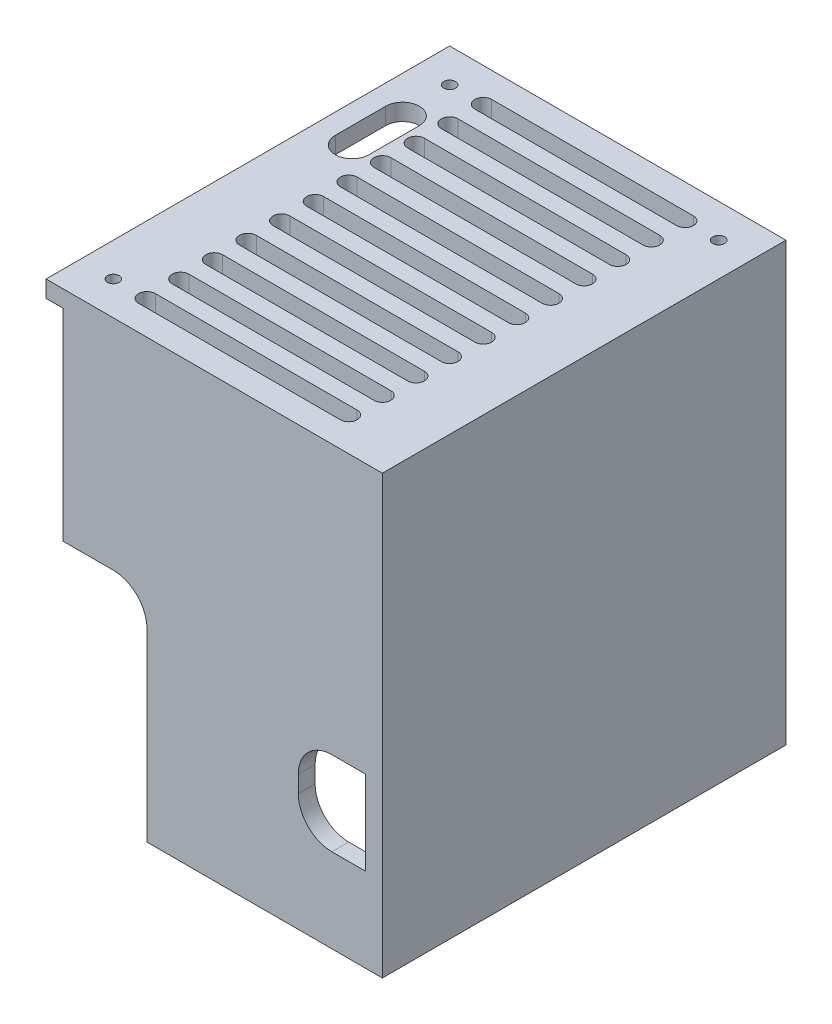
SolidWorks part; units mm, degrees
ref_plane "Front Plane" through (0, 0, 0) normal (0, 0, 1) x (1, 0, 0)
ref_plane "Top Plane" through (0, 0, 0) normal (0, 1, 0) x (1, 0, 0)
ref_plane "Right Plane" through (0, 0, 0) normal (1, 0, 0) x (0, 0, -1)
sketch "Sketch2" plane through (0, 0, 0) normal (0, 1, 0) x (1, 0, 0)
  line L1 (0, 0) -> (100, 0)
  line L2 (0, 0) -> (0, 120)
  line L3 (0, 120) -> (100, 120)
  line L4 (100, 0) -> (100, 120)
  line L5 (0, 0) -> (100, 120) construction
  line L6 (0, 120) -> (100, 0) construction
  point P4 (50, 60)
  dimension "D1" = 100
  dimension "D2" = 120
extrude "Boss-Extrude1" add sketch "Sketch2" along normal blind 5
sketch "Sketch3" plane through (0, 0, 0) normal (0, -1, 0) x (1, 0, 0)
  line L0 (0, 0) -> (100, 0) construction
  line L1 (100, 0) -> (95, 0)
  line L2 (100, 0) -> (100, -120)
  line L3 (100, -120) -> (95, -120)
  line L4 (95, 0) -> (95, -120)
  line L5 (100, 0) -> (95, -120) construction
  line L6 (100, -120) -> (95, 0) construction
  line L7 (100, -120) -> (0, -120) construction
  line L8 (100, 0) -> (100, -120) construction
  point P4 (97.5, -60)
  dimension "D1" = 5
extrude "Boss-Extrude2" add sketch "Sketch3" along normal blind 125
sketch "Sketch4" plane through (0, 0, 0) normal (0, -1, 0) x (1, 0, 0)
  line L0 (0, 0) -> (95, 0) construction
  line L1 (95, 0) -> (5, 0)
  line L2 (95, 0) -> (95, -5)
  line L3 (95, -5) -> (5, -5)
  line L4 (5, 0) -> (5, -5)
  line L5 (95, 0) -> (5, -5) construction
  line L6 (95, -5) -> (5, 0) construction
  line L7 (95, 0) -> (95, -120) construction
  point P4 (50, -2.5)
  dimension "D1" = 5
  dimension "D2" = 90
extrude "Boss-Extrude3" add sketch "Sketch4" along normal blind 125
sketch "Sketch5" plane through (0, -125, 0) normal (0, -1, 0) x (1, 0, 0)
  line L0 (95, -5) -> (95, -120) construction
  line L1 (95, -5) -> (85, -5)
  line L2 (95, -5) -> (95, -15)
  line L3 (95, -15) -> (85, -15)
  line L4 (85, -5) -> (85, -15)
  line L5 (95, -5) -> (85, -15) construction
  line L6 (95, -15) -> (85, -5) construction
  line L7 (5, -5) -> (95, -5) construction
  line L8 (95, -5) -> (95, -120) construction
  line L9 (95, -115) -> (85, -115)
  line L10 (95, -115) -> (95, -105)
  line L11 (95, -105) -> (85, -105)
  line L12 (85, -115) -> (85, -105)
  line L13 (95, -115) -> (85, -105) construction
  line L14 (95, -105) -> (85, -115) construction
  line L15 (95, -120) -> (0, -120) construction
  point P4 (90, -10)
  point P13 (90, -110)
  dimension "D1" = 10
  dimension "D2" = 10
  dimension "D3" = 10
  dimension "D4" = 10
  dimension "D5" = 5
extrude "Boss-Extrude4" add sketch "Sketch5" against normal blind 15
sketch "Sketch6" plane through (0, -125, 0) normal (0, -1, 0) x (1, 0, 0)
  line L0 (85, -15) -> (95, -15) construction
  line L1 (85, -5) -> (85, -15) construction
  line L2 (95, -105) -> (85, -105) construction
  line L3 (85, -105) -> (85, -115) construction
  circle A0 centre (90, -10) radius 1.45
  circle A1 centre (90, -110) radius 1.45
  dimension "D1" = 2.9
  dimension "D2" = 5
  dimension "D3" = 5
  dimension "D4" = 5
  dimension "D5" = 5
extrude "Cut-Extrude1" cut sketch "Sketch6" against normal blind 10
chamfer "Chamfer1" distance 10 angle 45 2 edges at (95, -110, -110) (95, -110, -10)
sketch "Sketch7" plane through (0, 0, 0) normal (0, -1, 0) x (1, 0, 0)
  line L0 (20, -10) -> (80, -10) construction
  line L1 (20, -7.5) -> (80, -7.5)
  line L2 (20, -12.5) -> (80, -12.5)
  line L3 (5, -5) -> (95, -5) construction
  line L4 (85, -5) -> (85, -15) construction
  line L5 (20, -20) -> (80, -20) construction
  line L6 (20, -17.5) -> (80, -17.5)
  line L7 (20, -22.5) -> (80, -22.5)
  line L8 (20, -30) -> (80, -30) construction
  line L9 (20, -27.5) -> (80, -27.5)
  line L10 (20, -32.5) -> (80, -32.5)
  line L11 (20, -40) -> (80, -40) construction
  line L12 (20, -37.5) -> (80, -37.5)
  line L13 (20, -42.5) -> (80, -42.5)
  line L14 (20, -50) -> (80, -50) construction
  line L15 (20, -47.5) -> (80, -47.5)
  line L16 (20, -52.5) -> (80, -52.5)
  line L17 (20, -60) -> (80, -60) construction
  line L18 (20, -57.5) -> (80, -57.5)
  line L19 (20, -62.5) -> (80, -62.5)
  line L20 (20, -70) -> (80, -70) construction
  line L21 (20, -67.5) -> (80, -67.5)
  line L22 (20, -72.5) -> (80, -72.5)
  line L23 (20, -80) -> (80, -80) construction
  line L24 (20, -77.5) -> (80, -77.5)
  line L25 (20, -82.5) -> (80, -82.5)
  line L26 (20, -90) -> (80, -90) construction
  line L27 (20, -87.5) -> (80, -87.5)
  line L28 (20, -92.5) -> (80, -92.5)
  line L29 (20, -100) -> (80, -100) construction
  line L30 (20, -97.5) -> (80, -97.5)
  line L31 (20, -102.5) -> (80, -102.5)
  line L32 (20, -110) -> (80, -110) construction
  line L33 (20, -107.5) -> (80, -107.5)
  line L34 (20, -112.5) -> (80, -112.5)
  line L35 (20, -10) -> (20, -20) construction
  arc A0 (20, -7.5) -> (20, -12.5) centre (20, -10) ccw
  arc A1 (80, -12.5) -> (80, -7.5) centre (80, -10) ccw
  arc A2 (20, -17.5) -> (20, -22.5) centre (20, -20) ccw
  arc A3 (80, -22.5) -> (80, -17.5) centre (80, -20) ccw
  arc A4 (20, -27.5) -> (20, -32.5) centre (20, -30) ccw
  arc A5 (80, -32.5) -> (80, -27.5) centre (80, -30) ccw
  arc A6 (20, -37.5) -> (20, -42.5) centre (20, -40) ccw
  arc A7 (80, -42.5) -> (80, -37.5) centre (80, -40) ccw
  arc A8 (20, -47.5) -> (20, -52.5) centre (20, -50) ccw
  arc A9 (80, -52.5) -> (80, -47.5) centre (80, -50) ccw
  arc A10 (20, -57.5) -> (20, -62.5) centre (20, -60) ccw
  arc A11 (80, -62.5) -> (80, -57.5) centre (80, -60) ccw
  arc A12 (20, -67.5) -> (20, -72.5) centre (20, -70) ccw
  arc A13 (80, -72.5) -> (80, -67.5) centre (80, -70) ccw
  arc A14 (20, -77.5) -> (20, -82.5) centre (20, -80) ccw
  arc A15 (80, -82.5) -> (80, -77.5) centre (80, -80) ccw
  arc A16 (20, -87.5) -> (20, -92.5) centre (20, -90) ccw
  arc A17 (80, -92.5) -> (80, -87.5) centre (80, -90) ccw
  arc A18 (20, -97.5) -> (20, -102.5) centre (20, -100) ccw
  arc A19 (80, -102.5) -> (80, -97.5) centre (80, -100) ccw
  arc A20 (20, -107.5) -> (20, -112.5) centre (20, -110) ccw
  arc A21 (80, -112.5) -> (80, -107.5) centre (80, -110) ccw
  point P2 (50, -10)
  point P14 (50, -20)
  point P21 (50, -30)
  point P28 (50, -40)
  point P35 (50, -50)
  point P42 (50, -60)
  point P49 (50, -70)
  point P56 (50, -80)
  point P63 (50, -90)
  point P70 (50, -100)
  point P77 (50, -110)
  dimension "D1" = 60
  dimension "D2" = 5
  dimension "D3" = 5
  dimension "D4" = 5
  dimension "D6" = 10
  dimension "D5" = 11
extrude "Cut-Extrude2" cut sketch "Sketch7" against normal blind 10
sketch "Sketch8" plane through (0, 0, 0) normal (0, 0, 1) x (1, 0, 0)
  line L0 (100, -125) -> (5, -125) construction
  line L1 (5, -125) -> (30, -125)
  line L2 (5, -125) -> (5, -60)
  line L3 (5, -60) -> (30, -60)
  line L4 (30, -125) -> (30, -60)
  line L5 (5, -125) -> (30, -60) construction
  line L6 (5, -60) -> (30, -125) construction
  line L7 (5, -125) -> (5, 0) construction
  point P4 (17.5, -92.5)
  dimension "D1" = 25
  dimension "D2" = 65
extrude "Cut-Extrude3" cut sketch "Sketch8" against normal blind 10
sketch "Sketch9" plane through (0, 0, 0) normal (0, -1, 0) x (1, 0, 0)
  circle A0 centre (10, -110) radius 1.75
  circle A1 centre (10, -10) radius 1.75
  circle A2 centre (90, -110) radius 1.75
  dimension "D1" = 3.5
extrude "Cut-Extrude4" cut sketch "Sketch9" against normal blind 10
sketch "Sketch10" plane through (0, 0, 0) normal (0, -1, 0) x (1, 0, 0)
  line L0 (11, -95) -> (11, -80) construction
  line L1 (6, -95) -> (6, -80)
  line L2 (16, -95) -> (16, -80)
  line L4 (95, -105) -> (85, -105) construction
  arc A0 (6, -95) -> (16, -95) centre (11, -95) ccw
  arc A1 (16, -80) -> (6, -80) centre (11, -80) ccw
  arc A2 (20, -87.5) -> (20, -92.5) centre (20, -90) ccw construction
  point P3 (11, -87.5)
  dimension "D3" = 4
  dimension "D1" = 15
  dimension "D2" = 10
  dimension "D4" = 10
extrude "Cut-Extrude5" cut sketch "Sketch10" against normal blind 10
sketch "Sketch11" plane through (0, 0, 0) normal (0, -1, 0) x (1, 0, 0)
  arc A0 (6, -80) -> (16, -80) centre (11, -77.5095) cw
  arc A1 (6, -80) -> (16, -80) centre (11, -80) cw
extrude "Boss-Extrude5" add sketch "Sketch11" along normal blind 20
sketch "Sketch12" plane through (0, 0, 0) normal (1, 0, 0) x (0, 0, -1)
  line L0 (71.9236, 0) -> (71.9236, -20) construction
  line L1 (72.9236, -7) -> (71.9236, -7)
  line L2 (72.9236, -7) -> (72.9236, -13)
  line L3 (72.9236, -13) -> (71.9236, -13)
  line L4 (71.9236, -7) -> (71.9236, -13)
  line L5 (72.9236, -7) -> (71.9236, -13) construction
  line L6 (72.9236, -13) -> (71.9236, -7) construction
  line L7 (71.9236, -20) -> (80, -20) construction
  point P4 (72.4236, -10)
  dimension "D1" = 1
  dimension "D2" = 13
  dimension "D3" = 6
extrude "Cut-Extrude6" cut sketch "Sketch12" along normal blind 40
chamfer "Chamfer2" distance 1 angle 45 2 edges at (11, -13, -72.9236) (11, -7, -72.9236)
sketch "Sketch13" plane through (95, 0, 0) normal (-1, 0, 0) x (0, 0, 1)
  circle A0 centre (-97.9, -110.9) radius 1.45
  circle A1 centre (-97.9, -9.1) radius 1.45
  circle A2 centre (-22.1, -9.1) radius 1.45
  circle A3 centre (-22.1, -110.9) radius 1.45
  circle A4 centre (-97.9, -110.9) radius 2.5
  circle A5 centre (-97.9, -9.1) radius 2.5
  circle A6 centre (-22.1, -9.1) radius 2.5
  circle A7 centre (-22.1, -110.9) radius 2.5
  dimension "D1" = 5
extrude "Boss-Extrude6" add sketch "Sketch13" along normal blind 3
chamfer "Chamfer3" distance 3 angle 45 4 edges at (95, -9.1, -100.4) (95, -9.1, -24.6) (95, -110.9, -24.6) (95, -110.9, -100.4)
sketch "Sketch14" plane through (0, 0, -5) normal (0, 0, -1) x (-1, 0, 0)
  line L0 (-95, -100) -> (-95, 0) construction
  line L1 (-95, -100) -> (-75, -100)
  line L2 (-95, -100) -> (-95, -75)
  line L3 (-95, -75) -> (-75, -75)
  line L4 (-75, -100) -> (-75, -75)
  line L5 (-95, -100) -> (-75, -75) construction
  line L6 (-95, -75) -> (-75, -100) construction
  point P4 (-85, -87.5)
  dimension "D1" = 25
  dimension "D2" = 20
extrude "Cut-Extrude7" cut sketch "Sketch14" against normal blind 10
fillet "Fillet1" radius 10 3 edges at (75, -100, -2.5) (75, -75, -2.5) (30, -60, -2.5)
